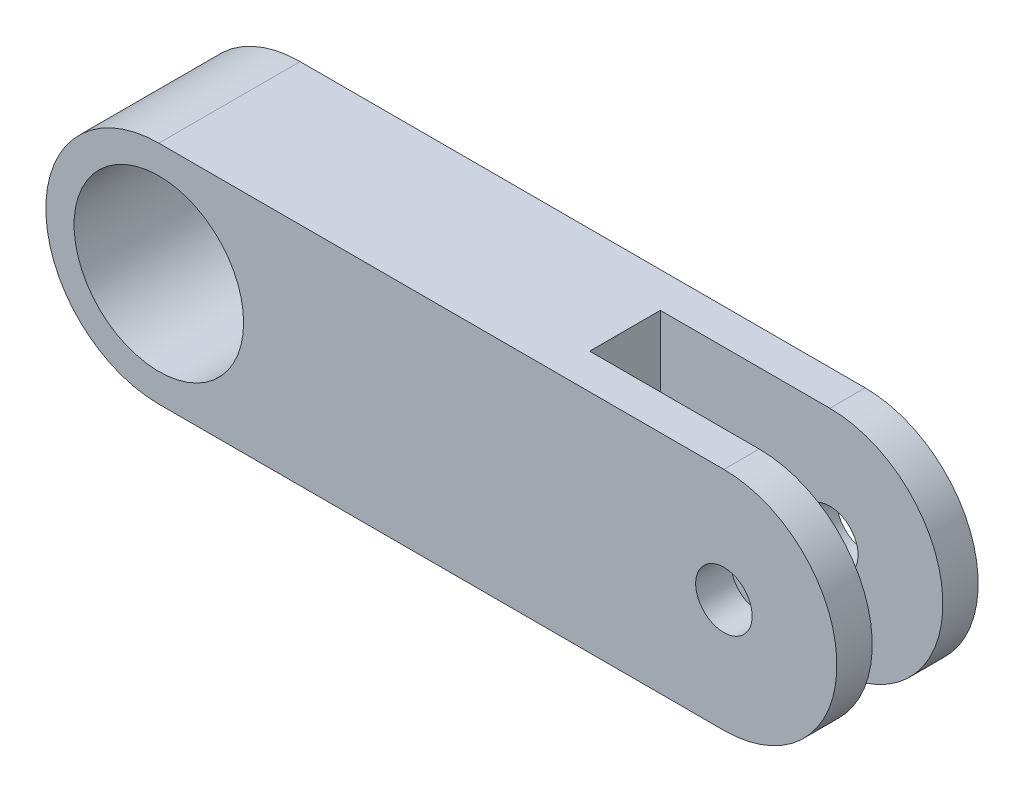
SolidWorks part; units mm, degrees
ref_plane "Front Plane" through (0, 0, 0) normal (0, 0, 1) x (1, 0, 0)
ref_plane "Top Plane" through (0, 0, 0) normal (0, 1, 0) x (1, 0, 0)
ref_plane "Right Plane" through (0, 0, 0) normal (1, 0, 0) x (0, 0, -1)
sketch "Sketch1" plane through (0, 0, 0) normal (0, 0, 1) x (1, 0, 0)
  line L0 (-10, 0) -> (10, 0) construction
  line L1 (-10, 4) -> (10, 4)
  line L2 (-10, -4) -> (10, -4)
  arc A0 (-10, 4) -> (-10, -4) centre (-10, 0) ccw
  arc A1 (10, -4) -> (10, 4) centre (10, 0) ccw
  circle A2 centre (-10, 0) radius 3
  circle A3 centre (10, 0) radius 1
  point P3 (0, 0)
  dimension "5.5" = 6
  dimension "D2" = 4
  dimension "D4" = 2
  dimension "D3" = 20
extrude "Boss-Extrude1" add sketch "Sketch1" along normal mid plane 5
sketch "Sketch5" plane through (0, 0, 0) normal (0, 0, 1) x (1, 0, 0)
  line L0 (10, 4) -> (-10, 4) construction
  line L1 (4, 4) -> (14, 4)
  line L2 (4, 4) -> (4, -4)
  line L3 (4, -4) -> (14, -4)
  line L4 (14, 4) -> (14, -4)
  line L5 (-10, -4) -> (10, -4) construction
  arc A0 (10, -4) -> (10, 4) centre (10, 0) ccw construction
  dimension "D1" = 10
extrude "Cut-Extrude1" cut sketch "Sketch5" against normal mid plane 2.5
